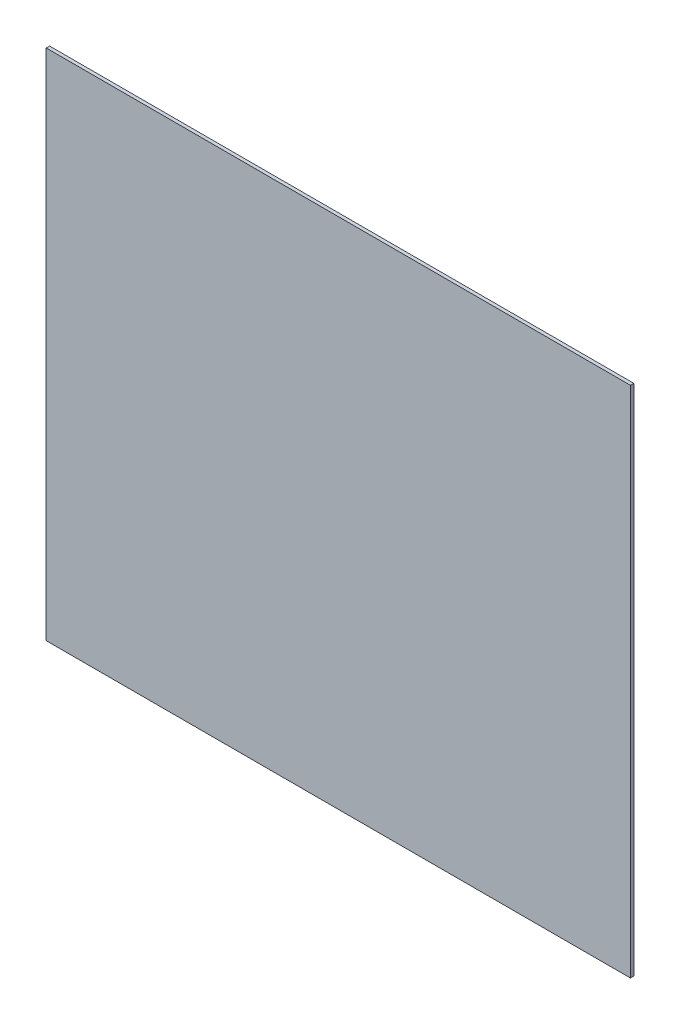
SolidWorks part; units mm, degrees
ref_plane "Front Plane" through (0, 0, 0) normal (0, 0, 1) x (1, 0, 0)
ref_plane "Top Plane" through (0, 0, 0) normal (0, 1, 0) x (1, 0, 0)
ref_plane "Right Plane" through (0, 0, 0) normal (1, 0, 0) x (0, 0, -1)
sketch "Sketch1" plane through (0, 0, 0) normal (0, 0, 1) x (1, 0, 0)
  line L1 (170, 152) -> (-170, 152)
  line L2 (170, 152) -> (170, -152)
  line L3 (170, -152) -> (-170, -152)
  line L4 (-170, 152) -> (-170, -152)
  line L5 (170, 152) -> (-170, -152) construction
  line L6 (170, -152) -> (-170, 152) construction
  line L7 (120, -128) -> (-128, -128)
  line L8 (127, -121) -> (127, 108)
  line L9 (120, 115) -> (-128, 115)
  line L10 (-135, -121) -> (-135, 108)
  line L11 (131, -117) -> (-131, 117) construction
  line L12 (131, 117) -> (-131, -117) construction
  line L13 (-170, 152) -> (-225, 152)
  line L14 (-170, 152) -> (-170, -152)
  line L15 (-170, -152) -> (-225, -152)
  line L16 (-225, 152) -> (-225, -152)
  line L17 (-197.5, -152) -> (-197.5, 152) construction
  line L18 (-170, 0) -> (-225, 0) construction
  line L19 (170, 152) -> (176, 152)
  line L20 (170, 152) -> (170, -152)
  line L21 (170, -152) -> (176, -152)
  line L22 (176, 152) -> (176, -152)
  line L23 (173, -152) -> (173, 152) construction
  line L24 (170, 0) -> (176, 0) construction
  arc A0 (-128, -128) -> (-135, -121) centre (-128, -121) cw
  arc A1 (120, -128) -> (127, -121) centre (120, -121) ccw
  arc A2 (127, 108) -> (120, 115) centre (120, 108) ccw
  arc A3 (-128, 115) -> (-135, 108) centre (-128, 108) ccw
  point P0 (0, 0)
  point P5 (0, 0)
  point P134 (-197.5, 0)
  point P253 (173, 0)
  dimension "D5" = 7
  dimension "D1" = 340
  dimension "D2" = 304
  dimension "D3" = 37
  dimension "D4" = 43
  dimension "D6" = 55
  dimension "D7" = 24
  dimension "D8" = 262
  dimension "D9" = 6
extrude "Boss-Extrude1" [suppressed] add sketch "Sketch1" along normal blind 2 contours L1 L4 L3 L2 A3 L9 A2 L8 A1 L7 A0 L10 | L13 L16 L15 L4
extrude "Boss-Extrude2" add sketch "Sketch1<3>" along normal blind 2 contours L1 L4 L3 L2 A3 L9 A2 L8 A1 L7 A0 L10 | L9 A3 L10 A0 L7 A1 L8 A2 | L22 L19 L2 L21 region at (165.4391, 0, 0) region at (173, 0, 0) region at (-4, -6.5, 0)
sketch "Sketch1<3>" plane through (0, 0, 0) normal (0, 0, 1) x (1, 0, 0) same geometry as "Sketch1"
